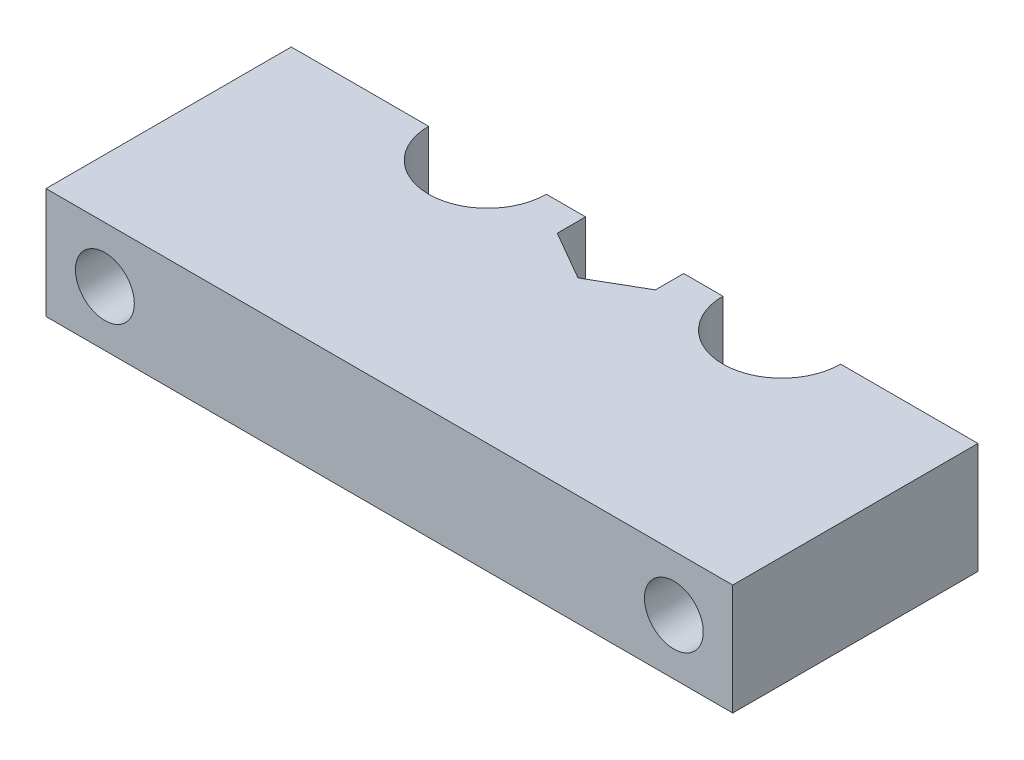
SolidWorks part; units mm, degrees
ref_plane "Front Plane" through (0, 0, 0) normal (0, 0, 1) x (1, 0, 0)
ref_plane "Top Plane" through (0, 0, 0) normal (0, 1, 0) x (1, 0, 0)
ref_plane "Right Plane" through (0, 0, 0) normal (1, 0, 0) x (0, 0, -1)
sketch "Sketch1" plane through (0, 0, 0) normal (0, 1, 0) x (1, 0, 0)
  line L0 (35, 0) -> (35, 25) construction
  line L1 (0, 0) -> (70, 0) construction
  line L2 (0, 0) -> (0, 25) construction
  line L3 (0, 25) -> (70, 25) construction
  line L4 (70, 0) -> (70, 25) construction
  line L5 (35, 19.2265) -> (40, 22.1132) construction
  line L6 (40, 22.1132) -> (40, 27.8868) construction
  line L7 (40, 27.8868) -> (35, 30.7735) construction
  line L8 (35, 30.7735) -> (30, 27.8868) construction
  line L9 (30, 27.8868) -> (30, 22.1132) construction
  line L10 (30, 22.1132) -> (35, 19.2265) construction
  line L11 (56, 25) -> (70, 25)
  line L12 (70, 25) -> (70, 0)
  line L13 (70, 0) -> (0, 0)
  line L14 (0, 0) -> (0, 25)
  line L15 (0, 25) -> (14, 25)
  line L16 (26, 25) -> (30, 25)
  line L21 (40, 25) -> (44, 25)
  line L22 (30, 25) -> (30, 22.1132)
  line L23 (30, 22.1132) -> (35, 19.2265)
  line L24 (35, 19.2265) -> (40, 22.1132)
  line L25 (40, 22.1132) -> (40, 25)
  circle A0 centre (35, 25) radius 5 construction
  circle A1 centre (20, 25) radius 6 construction
  circle A2 centre (50, 25) radius 6 construction
  arc A3 (14, 25) -> (26, 25) centre (20, 25) ccw
  arc A4 (44, 25) -> (56, 25) centre (50, 25) ccw
  dimension "D4" = 12
  dimension "D1" = 25
  dimension "D2" = 10
  dimension "D3" = 70
  dimension "D5" = 15
extrude "Boss-Extrude1" add sketch "Sketch1" along normal blind 11.3
sketch "Sketch2" plane through (0, 0, 0) normal (0, 0, 1) x (1, 0, 0)
  line L0 (35, 11.3) -> (35, 0) construction
  line L1 (0, 0) -> (70, 0) construction
  line L2 (0, 5.65) -> (6, 5.65) construction
  line L3 (0, 11.3) -> (0, 0) construction
  circle A0 centre (6, 5.65) radius 3
  circle A1 centre (64, 5.65) radius 3
  dimension "D2" = 6
  dimension "D1" = 6
extrude "Cut-Extrude1" cut sketch "Sketch2" against normal through all
